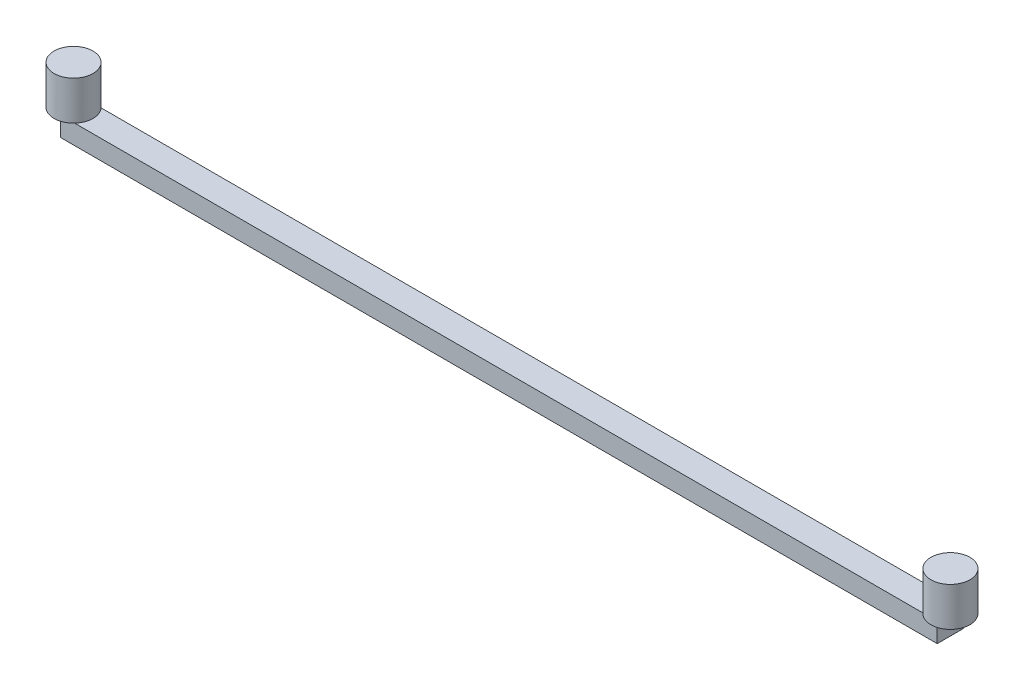
SolidWorks part; units mm, degrees
ref_plane "Front Plane" through (0, 0, 0) normal (0, 0, 1) x (1, 0, 0)
ref_plane "Top Plane" through (0, 0, 0) normal (0, 1, 0) x (1, 0, 0)
ref_plane "Right Plane" through (0, 0, 0) normal (1, 0, 0) x (0, 0, -1)
sketch "Sketch1" plane through (0, 0, 0) normal (0, 1, 0) x (1, 0, 0)
  line L1 (-57.15, -1.7253) -> (57.15, -1.7253)
  line L2 (-57.15, -1.7253) -> (-57.15, 1.7253)
  line L3 (-57.15, 1.7253) -> (57.15, 1.7253)
  line L4 (57.15, -1.7253) -> (57.15, 1.7253)
  line L5 (-57.15, -1.7253) -> (57.15, 1.7253) construction
  line L6 (-57.15, 1.7253) -> (57.15, -1.7253) construction
  point P0 (0, 0)
  dimension "D1" = 114.3
extrude "Boss-Extrude1" add sketch "Sketch1" along normal blind 2.54
sketch "Sketch2" plane through (0, 2.54, 0) normal (0, 1, 0) x (1, 0, 0)
  line L0 (-57.15, 1.7253) -> (-57.15, -1.7253) construction
  circle A0 centre (-57.15, 0) radius 2.54
  point P2 (-69.85, 0)
  dimension "D1" = 5.08
extrude "Boss-Extrude2" add sketch "Sketch2" along normal blind 5.08
sketch "Sketch3" plane through (0, 2.54, 0) normal (0, 1, 0) x (1, 0, 0)
  line L0 (57.15, -1.7253) -> (57.15, 1.7253) construction
  circle A0 centre (57.15, 0) radius 2.54
  point P2 (69.85, 0)
  dimension "D1" = 5.08
extrude "Boss-Extrude3" add sketch "Sketch3" along normal blind 5.08
